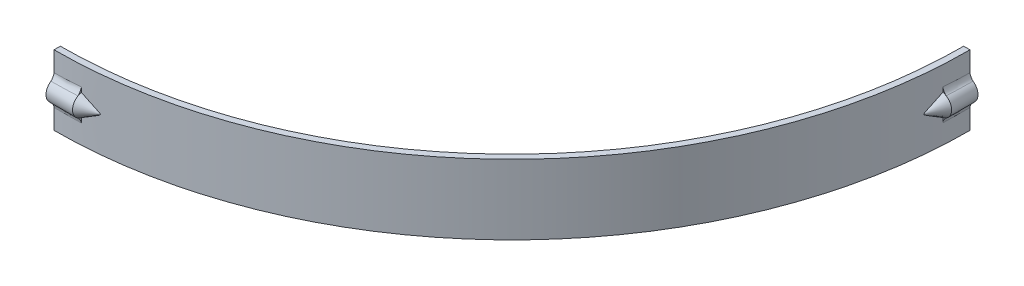
SolidWorks part; units mm, degrees
ref_plane "Front Plane" through (0, 0, 0) normal (0, 0, 1) x (1, 0, 0)
ref_plane "Top Plane" through (0, 0, 0) normal (0, 1, 0) x (1, 0, 0)
ref_plane "Right Plane" through (0, 0, 0) normal (1, 0, 0) x (0, 0, -1)
sketch "Sketch1" plane through (0, 0, 0) normal (0, 0, 1) x (1, 0, 0)
  line L0 (0, 3.3639) -> (0, -36.2756) construction
  line L1 (166.5732, 12.7) -> (164.2872, 12.7)
  line L2 (166.5732, 12.7) -> (166.5732, -12.7)
  line L3 (166.5732, -12.7) -> (164.2872, -12.7)
  line L4 (164.2872, 12.7) -> (164.2872, -12.7)
  line L5 (166.5732, 12.7) -> (164.2872, -12.7) construction
  line L6 (166.5732, -12.7) -> (164.2872, 12.7) construction
  point P0 (165.4302, 0)
  dimension "D1" = 25.4
  dimension "D2" = 2.286
  dimension "D3" = 165.4302
revolve "Revolve1" add sketch "Sketch1" angle 90 about L0
sketch "Sketch4" plane through (0, 0, 0) normal (-1, 0, 0) x (0, 0, 1)
  line L1 (166.5732, 12.7) -> (164.2872, 12.7) construction
  circle A0 centre (165.4302, 0) radius 4.064
  point P2 (0, 0)
  point P5 (165.4302, 12.7)
  dimension "D2" = 8.128
extrude "Boss-Extrude1" add sketch "Sketch4" against normal blind 9.652
sketch "Sketch6" plane through (9.652, 0, 0) normal (1, 0, 0) x (0, 0, -1)
  circle A0 centre (-165.4302, 0) radius 3.175
  circle A2 centre (-165.4302, 0) radius 4.064 construction
  dimension "D1" = 6.35
fillet "Fillet6" radius 2.54 2 edges at (8.128, 3.9527, 166.3748) (1.5264, -3.902, 166.5662)
fillet "Fillet8" radius 2.54 2 edges at (8.128, -3.8353, 164.086) (1.5263, 3.8979, 164.2801)
sketch "Sketch7" plane through (0, 0, 0) normal (0, 0, -1) x (-1, 0, 0)
  line L1 (-166.5732, 12.7) -> (-164.2872, 12.7) construction
  circle A0 centre (-165.4302, 0) radius 4.064
  point P2 (0, 0)
  point P5 (0, 0)
  point P6 (0, 0)
  point P7 (-165.4302, 12.7)
  point P8 (0, 0)
  dimension "D1" = 8.128
extrude "Boss-Extrude2" add sketch "Sketch7" against normal blind 9.6012
sketch "Sketch8" plane through (0, 0, 9.6012) normal (0, 0, 1) x (1, 0, 0)
  circle A0 centre (165.4302, 0) radius 3.175
  circle A1 centre (165.4302, 0) radius 4.064 construction
  dimension "D1" = 6.35
fillet "Fillet11" radius 2.54 4 edges at (164.086, 3.8353, 8.128) (164.2806, -3.898, 1.4754) (166.3748, -3.9527, 8.128) (166.5667, 3.9019, 1.4755)
sketch "Sketch9" plane through (0, 0, 0) normal (-1, 0, 0) x (0, 0, 1)
  circle A0 centre (165.4302, 0) radius 3.3655
  dimension "D1" = 6.731
extrude "Cut-Extrude1" cut sketch "Sketch9" against normal blind 9.525
sketch "Sketch10" plane through (0, 0, 0) normal (0, 0, -1) x (-1, 0, 0)
  circle A0 centre (-165.4302, 0) radius 3.3655
  dimension "D1" = 6.731
extrude "Cut-Extrude2" cut sketch "Sketch10" against normal blind 9.525
sketch "Sketch11" plane through (0, 0, 0) normal (0, 1, 0) x (1, 0, 0)
  line L0 (9.652, -161.3662) -> (9.652, -165.3032)
  line L1 (9.652, -169.4942) -> (16.4711, -165.5572)
  line L2 (16.4711, -165.3032) -> (9.652, -161.3662)
  line L3 (9.652, -165.4302) -> (13.6215, -165.4302) construction
  line L4 (9.652, -165.3032) -> (16.4711, -165.3032)
  line L5 (16.4711, -165.5572) -> (9.652, -165.5572)
  line L6 (9.652, -165.5572) -> (9.652, -169.4942)
  line L7 (9.652, -168.6052) -> (9.652, -162.2552) construction
  dimension "D1" = 60
  dimension "D2" = 60
  dimension "D3" = 0.254
revolve "Revolve7" add sketch "Sketch11" angle 180 about L3
sketch "Sketch12" plane through (0, 0, 0) normal (0, 1, 0) x (1, 0, 0)
  line L0 (161.3662, -9.6012) -> (165.3032, -16.4203)
  line L1 (165.5572, -16.4203) -> (169.4942, -9.6012)
  line L2 (167.5288, -9.6012) -> (169.4942, -9.6012) construction
  line L3 (169.4942, -9.6012) -> (165.5572, -9.6012)
  line L4 (165.5572, -9.6012) -> (165.5572, -16.4203)
  line L6 (165.3032, -16.4203) -> (165.3032, -9.6012)
  line L7 (165.4302, -9.9069) -> (165.4302, -14.0613) construction
  line L8 (165.3032, -9.6012) -> (161.3662, -9.6012)
  dimension "D1" = 60
  dimension "D2" = 60
  dimension "D3" = 0.254
revolve "Revolve8" add sketch "Sketch12" angle 203 about L7
